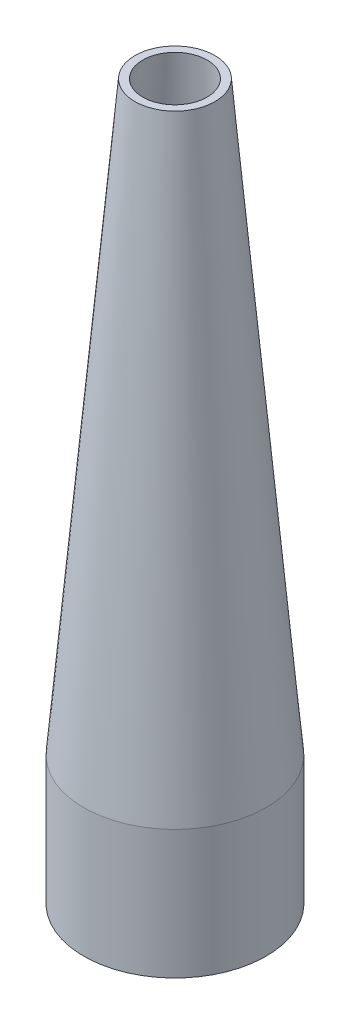
SolidWorks part; units mm, degrees
material "S-Glass Fiber"
ref_plane "Front Plane" through (0, 0, 0) normal (0, 0, 1) x (1, 0, 0)
ref_plane "Top Plane" through (0, 0, 0) normal (0, 1, 0) x (1, 0, 0)
ref_plane "Right Plane" through (0, 0, 0) normal (1, 0, 0) x (0, 0, -1)
sketch "Sketch1" plane through (0, 0, 0) normal (0, 0, 1) x (1, 0, 0)
  line L0 (0, 0) -> (0, 53.5349) construction
  line L1 (9.525, 53.5349) -> (11.8197, 53.5349)
  line L2 (11.8197, 53.5349) -> (26.9875, -119.8334)
  line L3 (26.9875, -119.8334) -> (24.6928, -119.8334)
  line L4 (24.6928, -119.8334) -> (9.525, 53.5349)
  line L6 (24.6928, -119.8334) -> (26.9875, -119.8334)
  line L7 (24.6928, -119.8334) -> (24.6928, -157.9334)
  line L8 (24.6928, -157.9334) -> (26.9875, -157.9334)
  line L9 (26.9875, -119.8334) -> (26.9875, -157.9334)
  line L10 (26.9875, -157.9334) -> (26.9875, -907.2334) construction
  point P11 (26.9875, -157.9334)
  point P15 (24.3103, -157.9334)
revolve "Revolve1" add sketch "Sketch1" angle 360 about L0 region at (18.2563, -33.1493, 0) region at (25.8401, -138.8834, 0)
